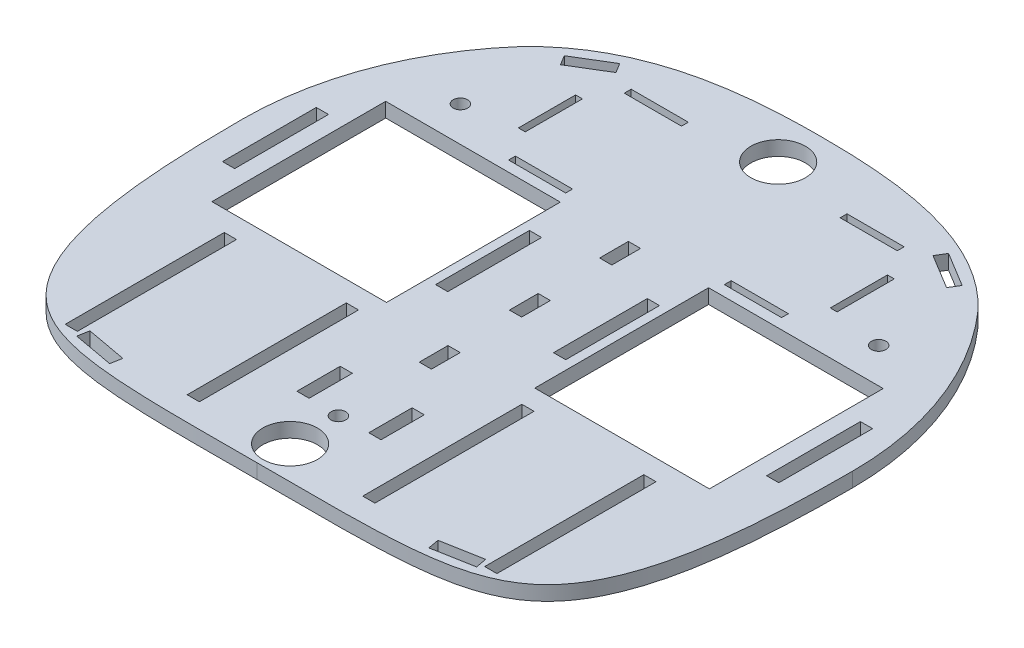
SolidWorks part; units mm, degrees
ref_plane "Front Plane" through (0, 0, 0) normal (0, 0, 1) x (1, 0, 0)
ref_plane "Top Plane" through (0, 0, 0) normal (0, 1, 0) x (1, 0, 0)
ref_plane "Right Plane" through (0, 0, 0) normal (1, 0, 0) x (0, 0, -1)
sketch "Sketch1" plane through (0, 0, 0) normal (0, 1, 0) x (1, 0, 0)
  line L0 (0, 0) -> (-157.9039, -157.9039) construction
  line L1 (0, -127) -> (0, 133.35) construction
  arc A0 (133.35, 0) -> (-133.35, 0) centre (0, 0) ccw
  spline S0 degree 3 poles (-133.35, 0) (-133.35, -51.198) (-123.8034, -129.8051) (-58.428, -127) (0, -127) knots 0 0 0 0 0.502616 1 1 1 1
  spline S1 degree 3 poles (133.35, 0) (133.35, -51.198) (123.8034, -129.8051) (58.428, -127) (0, -127) knots 0 0 0 0 0.502616 1 1 1 1
  dimension "D1" = 266.7
extrude "Base" add sketch "Sketch1" along normal blind 6.35
sketch "ShaftLayout" plane through (0, 6.35, 0) normal (0, 1, 0) x (1, 0, 0)
  line L0 (-133.35, 0) -> (133.35, 0) construction
  line L1 (0, 133.35) -> (0, -127) construction
  line L2 (-114.7053, -6.35) -> (-104.7993, -6.35)
  line L3 (-36.3853, -38) -> (-94.3853, -38)
  line L4 (-36.3853, -38) -> (-36.3853, 38)
  line L5 (-36.3853, 38) -> (-94.3853, 38)
  line L6 (-94.3853, -38) -> (-94.3853, 38)
  line L7 (-36.3853, -38) -> (-94.3853, 38) construction
  line L8 (-36.3853, 38) -> (-94.3853, -38) construction
  line L9 (-102.0053, -15.875) -> (-104.7993, -15.875)
  line L10 (-102.0053, -15.875) -> (-102.0053, 15.875)
  line L11 (-102.0053, 15.875) -> (-104.7993, 15.875)
  line L12 (-104.7993, -15.875) -> (-104.7993, 15.875)
  line L13 (-102.0053, -15.875) -> (-104.7993, 15.875) construction
  line L14 (-102.0053, 15.875) -> (-104.7993, -15.875) construction
  line L15 (-114.7053, -6.35) -> (-114.7053, 6.35)
  line L16 (-104.7993, -6.35) -> (-104.7993, 6.35)
  line L17 (-114.7053, 6.35) -> (-104.7993, 6.35)
  line L18 (-114.7053, -6.35) -> (-104.7993, 6.35) construction
  line L19 (-104.7993, -6.35) -> (-114.7053, 6.35) construction
  line L20 (-116.2928, -9.525) -> (-114.7053, -9.525)
  line L21 (-116.2928, -9.525) -> (-116.2928, 9.525)
  line L22 (-114.7053, -9.525) -> (-114.7053, 9.525)
  line L23 (-116.2928, 9.525) -> (-114.7053, 9.525)
  line L24 (-116.2928, -9.525) -> (-114.7053, 9.525) construction
  line L25 (-114.7053, -9.525) -> (-116.2928, 9.525) construction
  line L26 (-127.4053, -7.9375) -> (-116.2928, -7.9375)
  line L27 (-127.4053, -7.9375) -> (-127.4053, 7.9375)
  line L28 (-116.2928, -7.9375) -> (-116.2928, 7.9375)
  line L29 (-127.4053, 7.9375) -> (-116.2928, 7.9375)
  line L30 (-127.4053, -7.9375) -> (-116.2928, 7.9375) construction
  line L31 (-116.2928, -7.9375) -> (-127.4053, 7.9375) construction
  line L32 (-17.3353, -7.9375) -> (-28.4478, -7.9375)
  line L33 (-30.0353, -9.525) -> (-28.4478, -9.525)
  line L34 (-30.0353, -9.525) -> (-30.0353, 9.525)
  line L35 (-30.0353, 9.525) -> (-28.4478, 9.525)
  line L36 (-28.4478, -9.525) -> (-28.4478, 9.525)
  line L37 (-30.0353, -9.525) -> (-28.4478, 9.525) construction
  line L38 (-30.0353, 9.525) -> (-28.4478, -9.525) construction
  line L39 (-17.3353, -7.9375) -> (-17.3353, 7.9375)
  line L40 (-28.4478, -7.9375) -> (-28.4478, 7.9375)
  line L41 (-17.3353, 7.9375) -> (-28.4478, 7.9375)
  line L42 (-17.3353, -7.9375) -> (-28.4478, 7.9375) construction
  line L43 (-28.4478, -7.9375) -> (-17.3353, 7.9375) construction
  line L45 (-67.3853, -10.033) -> (-56.3853, -10.033)
  line L46 (-67.3853, -10.033) -> (-67.3853, 10.033)
  line L47 (-67.3853, 10.033) -> (-56.3853, 10.033)
  line L48 (-56.3853, -10.033) -> (-56.3853, 10.033)
  line L49 (-67.3853, -10.033) -> (-56.3853, 10.033) construction
  line L50 (-67.3853, 10.033) -> (-56.3853, -10.033) construction
  arc A0 (133.35, 0) -> (-133.35, 0) centre (0, 0) ccw construction
  point P10 (-65.3853, 0)
  point P15 (-103.4023, 0)
  point P20 (-29.2416, 0)
  point P21 (-109.7523, 0)
  point P22 (-115.4991, 0)
  point P23 (-121.8491, 0)
  point P40 (-61.8853, 0)
  point P41 (-22.8916, 0)
  dimension "D1" = 58
  dimension "D2" = 76
  dimension "D3" = 7.62
  dimension "D4" = 2.794
  dimension "D5" = 31.75
  dimension "D6" = 9.906
  dimension "D7" = 12.7
  dimension "D8" = 19.05
  dimension "D9" = 1.5875
  dimension "D10" = 12.7
  dimension "D11" = 15.875
  dimension "D12" = 19.05
  dimension "D13" = 1.5875
  dimension "D14" = 15.875
  dimension "D15" = 12.7
  dimension "D16" = 6.35
  dimension "D17" = 20.066
  dimension "D18" = 20
  dimension "D19" = 11
sketch "MotorLayout" plane through (0, 6.35, 0) normal (0, 1, 0) x (1, 0, 0)
  line L0 (-94.3853, -81.74) -> (-114.3853, -81.74) construction
  line L1 (-94.3853, -110.24) -> (-18.3853, -110.24)
  line L2 (-94.3853, -110.24) -> (-94.3853, -53.24)
  line L3 (-94.3853, -53.24) -> (-18.3853, -53.24)
  line L4 (-18.3853, -110.24) -> (-18.3853, -53.24)
  line L5 (-94.3853, -110.24) -> (-18.3853, -53.24) construction
  line L6 (-94.3853, -53.24) -> (-18.3853, -110.24) construction
  line L7 (-114.7053, -92.0587) -> (-104.7993, -92.0587)
  line L8 (-104.7993, -97.615) -> (-102.0053, -97.615)
  line L9 (-104.7993, -97.615) -> (-104.7993, -65.865)
  line L10 (-104.7993, -65.865) -> (-102.0053, -65.865)
  line L11 (-102.0053, -97.615) -> (-102.0053, -65.865)
  line L12 (-104.7993, -97.615) -> (-102.0053, -65.865) construction
  line L13 (-104.7993, -65.865) -> (-102.0053, -97.615) construction
  line L14 (-36.3853, -38) -> (-94.3853, -38) construction
  line L15 (-114.7053, -92.0587) -> (-114.7053, -71.4212)
  line L16 (-104.7993, -92.0587) -> (-104.7993, -71.4212)
  line L17 (-114.7053, -71.4212) -> (-104.7993, -71.4212)
  line L18 (-114.7053, -92.0587) -> (-104.7993, -71.4212) construction
  line L19 (-104.7993, -92.0587) -> (-114.7053, -71.4212) construction
  line L20 (-103.4023, -1000) -> (-103.4023, 49000) construction
  line L21 (-34.8953, -53.24) -> (-34.8953, -110.24) construction
  point P0 (-56.3853, -81.74)
  point P7 (-103.4023, -81.74)
  point P14 (-109.7523, -81.74)
  dimension "D1" = 20
  dimension "D2" = 76
  dimension "D3" = 57
  dimension "D4" = 2.794
  dimension "D5" = 15.24
  dimension "D6" = 31.75
  dimension "D7" = 20.6375
  dimension "D8" = 12.7
  dimension "D9" = 7.62
  dimension "D10" = 16.51
sketch "Sketch6" plane through (0, 6.35, 0) normal (0, 1, 0) x (1, 0, 0)
  line L0 (-36.3853, -38) -> (-36.3853, 38) construction
  line L1 (-32.4166, -38) -> (-108.7681, -38)
  line L2 (-32.4166, -38) -> (-32.4166, 38)
  line L3 (-32.4166, 38) -> (-108.7681, 38)
  line L4 (-108.7681, -38) -> (-108.7681, 38)
  line L5 (-28.4478, -9.525) -> (-28.4478, 9.525) construction
  line L6 (-104.7993, -15.875) -> (-104.7993, 15.875) construction
  line L7 (0, 133.35) -> (0, -127) construction
  line L8 (28.4478, 20.5105) -> (23.1138, -20.5105) construction
  line L9 (28.4478, -20.5105) -> (23.1138, 20.5105) construction
  line L10 (116.2928, 20.5105) -> (121.6268, -20.5105) construction
  line L11 (116.2928, -20.5105) -> (121.6268, 20.5105) construction
  line L12 (-133.35, 0) -> (133.35, 0) construction
  line L13 (-116.2928, -20.5105) -> (-121.6268, -20.5105)
  line L14 (-116.2928, -20.5105) -> (-116.2928, 20.5105)
  line L15 (-116.2928, 20.5105) -> (-121.6268, 20.5105)
  line L16 (-121.6268, -20.5105) -> (-121.6268, 20.5105)
  line L17 (-116.2928, -20.5105) -> (-121.6268, 20.5105) construction
  line L18 (-116.2928, 20.5105) -> (-121.6268, -20.5105) construction
  line L19 (-116.2928, -9.525) -> (-116.2928, 9.525) construction
  line L20 (-127.4053, 7.9375) -> (-116.2928, 7.9375) construction
  line L21 (-17.3353, 7.9375) -> (-28.4478, 7.9375) construction
  line L22 (-28.4478, -20.5105) -> (-23.1138, -20.5105)
  line L23 (-28.4478, -20.5105) -> (-28.4478, 20.5105)
  line L24 (-28.4478, 20.5105) -> (-23.1138, 20.5105)
  line L25 (-23.1138, -20.5105) -> (-23.1138, 20.5105)
  line L26 (-28.4478, -20.5105) -> (-23.1138, 20.5105) construction
  line L27 (-28.4478, 20.5105) -> (-23.1138, -20.5105) construction
  line L28 (23.1138, -20.5105) -> (23.1138, 20.5105)
  line L29 (28.4478, 20.5105) -> (23.1138, 20.5105)
  line L30 (28.4478, -20.5105) -> (28.4478, 20.5105)
  line L31 (28.4478, -20.5105) -> (23.1138, -20.5105)
  line L32 (121.6268, -20.5105) -> (121.6268, 20.5105)
  line L33 (116.2928, 20.5105) -> (121.6268, 20.5105)
  line L34 (116.2928, -20.5105) -> (116.2928, 20.5105)
  line L35 (116.2928, -20.5105) -> (121.6268, -20.5105)
  line L36 (108.7681, -38) -> (108.7681, 38)
  line L37 (32.4166, 38) -> (108.7681, 38)
  line L38 (32.4166, -38) -> (32.4166, 38)
  line L39 (32.4166, -38) -> (108.7681, -38)
  point P16 (-118.9598, 0)
  point P27 (-25.7808, 0)
  point P44 (25.7808, 0)
  point P45 (118.9598, 0)
  dimension "D1" = 3.9688
  dimension "D2" = 3.9688
  dimension "D3" = 12.573
  dimension "D4" = 12.573
  dimension "D5" = 5.334
  dimension "D6" = 5.334
extrude "WheelShaftCut" cut sketch "Sketch6" against normal through all
sketch "Sketch8" plane through (0, 6.35, 0) normal (0, 1, 0) x (1, 0, 0)
  line L0 (-94.3853, -81.74) -> (-18.3853, -81.74) construction
  line L1 (-18.3853, -110.24) -> (-18.3853, -53.24) construction
  line L2 (-94.3853, -53.24) -> (-18.3853, -53.24) construction
  line L3 (-35.7113, -116.5265) -> (-41.0453, -116.5265)
  line L4 (-35.7113, -116.5265) -> (-35.7113, -46.9535)
  line L5 (-35.7113, -46.9535) -> (-41.0453, -46.9535)
  line L6 (-41.0453, -116.5265) -> (-41.0453, -46.9535)
  line L7 (-35.7113, -116.5265) -> (-41.0453, -46.9535) construction
  line L8 (-35.7113, -46.9535) -> (-41.0453, -116.5265) construction
  line L9 (18.3853, -72.2785) -> (13.0513, -91.2015) construction
  line L10 (18.3853, -91.2015) -> (13.0513, -72.2785) construction
  line L11 (18.3853, -81.74) -> (15.7183, -81.74) construction
  line L12 (89.0513, -46.9535) -> (94.3853, -116.5265) construction
  line L13 (89.0513, -116.5265) -> (94.3853, -46.9535) construction
  line L14 (35.7113, -46.9535) -> (41.0453, -116.5265) construction
  line L15 (-89.0513, -116.5265) -> (-94.3853, -116.5265)
  line L16 (-89.0513, -116.5265) -> (-89.0513, -46.9535)
  line L17 (-89.0513, -46.9535) -> (-94.3853, -46.9535)
  line L18 (-94.3853, -116.5265) -> (-94.3853, -46.9535)
  line L19 (-89.0513, -116.5265) -> (-94.3853, -46.9535) construction
  line L20 (-89.0513, -46.9535) -> (-94.3853, -116.5265) construction
  line L21 (-94.3853, -110.24) -> (-94.3853, -53.24) construction
  line L22 (0, 133.35) -> (0, -127) construction
  line L23 (35.7113, -116.5265) -> (41.0453, -46.9535) construction
  line L24 (94.3853, -81.74) -> (18.3853, -81.74) construction
  line L25 (13.0513, -91.2015) -> (13.0513, -72.2785)
  line L26 (18.3853, -72.2785) -> (13.0513, -72.2785)
  line L27 (18.3853, -91.2015) -> (18.3853, -72.2785)
  line L28 (18.3853, -91.2015) -> (13.0513, -91.2015)
  line L29 (94.3853, -116.5265) -> (94.3853, -46.9535)
  line L30 (89.0513, -46.9535) -> (94.3853, -46.9535)
  line L31 (89.0513, -116.5265) -> (89.0513, -46.9535)
  line L32 (89.0513, -116.5265) -> (94.3853, -116.5265)
  line L33 (41.0453, -116.5265) -> (41.0453, -46.9535)
  line L34 (35.7113, -46.9535) -> (41.0453, -46.9535)
  line L35 (35.7113, -116.5265) -> (35.7113, -46.9535)
  line L36 (35.7113, -116.5265) -> (41.0453, -116.5265)
  line L37 (-94.3853, -110.24) -> (-18.3853, -110.24) construction
  line L42 (-18.3853, -81.74) -> (-15.7183, -81.74) construction
  line L44 (-18.3853, -91.2015) -> (-13.0513, -91.2015)
  line L45 (-18.3853, -91.2015) -> (-18.3853, -72.2785)
  line L46 (-18.3853, -72.2785) -> (-13.0513, -72.2785)
  line L47 (-13.0513, -91.2015) -> (-13.0513, -72.2785)
  line L48 (-18.3853, -91.2015) -> (-13.0513, -72.2785) construction
  line L49 (-18.3853, -72.2785) -> (-13.0513, -91.2015) construction
  point P6 (-63.7079, -81.74)
  point P7 (-38.2513, -81.74)
  point P19 (-91.5913, -81.74)
  point P39 (91.5913, -81.74)
  point P40 (38.2513, -81.74)
  dimension "D1" = 5.334
  dimension "D2" = 6.2865
  dimension "D4" = 5.334
  dimension "D5" = 18.923
  dimension "D6" = 6.2865
  dimension "D3" = 2
extrude "MotorCut" cut sketch "Sketch8" against normal through all
sketch "BatteryLayout" plane through (0, 6.35, 0) normal (0, 1, 0) x (1, 0, 0)
  line L0 (0, 133.35) -> (0, -127) construction
  line L1 (-32.4166, 38) -> (-108.7681, 38) construction
  line L2 (-66.675, 45.62) -> (66.675, 45.62)
  line L3 (-66.675, 45.62) -> (-66.675, 93.245)
  line L4 (-66.675, 93.245) -> (66.675, 93.245)
  line L5 (66.675, 45.62) -> (66.675, 93.245)
  line L6 (-66.675, 45.62) -> (66.675, 93.245) construction
  line L7 (-66.675, 93.245) -> (66.675, 45.62) construction
  arc A0 (133.35, 0) -> (-133.35, 0) centre (0, 0) ccw construction
  point P6 (0, 69.4325)
  dimension "D1" = 133.35
  dimension "D2" = 47.625
  dimension "D3" = 7.62
sketch "Sketch10" plane through (0, 6.35, 0) normal (0, 1, 0) x (1, 0, 0)
  line L0 (-66.675, 93.245) -> (66.675, 93.245) construction
  line L1 (-59.69, 42.62) -> (-34.69, 42.62)
  line L2 (-59.69, 42.62) -> (-59.69, 45.62)
  line L3 (-59.69, 45.62) -> (-34.69, 45.62)
  line L4 (-34.69, 42.62) -> (-34.69, 45.62)
  line L5 (-59.69, 42.62) -> (-34.69, 45.62) construction
  line L6 (-59.69, 45.62) -> (-34.69, 42.62) construction
  line L7 (-59.69, 96.245) -> (-34.69, 96.245)
  line L8 (-59.69, 96.245) -> (-59.69, 93.245)
  line L9 (-59.69, 93.245) -> (-34.69, 93.245)
  line L10 (-34.69, 96.245) -> (-34.69, 93.245)
  line L11 (-59.69, 96.245) -> (-34.69, 93.245) construction
  line L12 (-59.69, 93.245) -> (-34.69, 96.245) construction
  line L13 (-66.675, 45.62) -> (66.675, 45.62) construction
  line L14 (-66.675, 45.62) -> (-66.675, 93.245) construction
  line L15 (0, 69.4325) -> (-66.675, 69.4325) construction
  line L16 (-66.675, 56.9325) -> (-69.675, 56.9325)
  line L17 (-66.675, 56.9325) -> (-66.675, 81.9325)
  line L18 (-66.675, 81.9325) -> (-69.675, 81.9325)
  line L19 (-69.675, 56.9325) -> (-69.675, 81.9325)
  line L20 (0, 133.35) -> (0, -127) construction
  line L21 (59.69, 93.245) -> (34.69, 96.245) construction
  line L22 (59.69, 96.245) -> (34.69, 93.245) construction
  line L23 (59.69, 45.62) -> (34.69, 42.62) construction
  line L24 (59.69, 42.62) -> (34.69, 45.62) construction
  line L25 (69.675, 56.9325) -> (69.675, 81.9325)
  line L26 (66.675, 81.9325) -> (69.675, 81.9325)
  line L27 (66.675, 56.9325) -> (66.675, 81.9325)
  line L28 (66.675, 56.9325) -> (69.675, 56.9325)
  line L29 (34.69, 96.245) -> (34.69, 93.245)
  line L30 (59.69, 93.245) -> (34.69, 93.245)
  line L31 (59.69, 96.245) -> (59.69, 93.245)
  line L32 (59.69, 96.245) -> (34.69, 96.245)
  line L33 (34.69, 42.62) -> (34.69, 45.62)
  line L34 (59.69, 45.62) -> (34.69, 45.62)
  line L35 (59.69, 42.62) -> (59.69, 45.62)
  line L36 (59.69, 42.62) -> (34.69, 42.62)
  point P0 (-47.19, 44.12)
  point P5 (-47.19, 94.745)
  point P20 (-66.675, 69.4325)
  point P40 (66.675, 69.4325)
  point P41 (47.19, 94.745)
  point P42 (47.19, 44.12)
  dimension "D1" = 3
  dimension "D2" = 3
  dimension "D3" = 25
  dimension "D4" = 25
  dimension "D5" = 6.985
  dimension "D6" = 6.985
  dimension "D7" = 3
  dimension "D8" = 25
extrude "VelcroCut" cut sketch "Sketch10" against normal through all
sketch "Sketch11" plane through (0, 6.35, 0) normal (0, 1, 0) x (1, 0, 0)
  line L0 (0, 133.35) -> (0, -127) construction
  line L1 (-133.35, 0) -> (133.35, 0) construction
  circle A1 centre (0, -91.44) radius 3.175
  circle A2 centre (-91.44, 53.34) radius 3.175
  circle A3 centre (91.44, 53.34) radius 3.175
  dimension "D1" = 6.35
  dimension "D2" = 53.34
  dimension "D3" = 6.35
  dimension "D6" = 91.44
  dimension "D4" = 91.44
extrude "ScrewCut" cut sketch "Sketch11" against normal through all
sketch "Sketch13" plane through (0, 6.35, 0) normal (0, 1, 0) x (1, 0, 0)
  line L0 (0, 133.35) -> (0, -127) construction
  line L1 (-2.667, 25.427) -> (2.667, 25.427)
  line L2 (-2.667, 25.427) -> (-2.667, 38)
  line L3 (-2.667, 38) -> (2.667, 38)
  line L4 (2.667, 25.427) -> (2.667, 38)
  line L5 (-2.667, 25.427) -> (2.667, 38) construction
  line L6 (-2.667, 38) -> (2.667, 25.427) construction
  line L7 (108.7681, 38) -> (32.4166, 38) construction
  line L8 (-2.667, -14.0065) -> (2.667, -14.0065)
  line L9 (-2.667, -14.0065) -> (-2.667, -1.4335)
  line L10 (-2.667, -1.4335) -> (2.667, -1.4335)
  line L11 (2.667, -14.0065) -> (2.667, -1.4335)
  line L12 (-2.667, -14.0065) -> (2.667, -1.4335) construction
  line L13 (-2.667, -1.4335) -> (2.667, -14.0065) construction
  line L14 (-2.667, -53.44) -> (2.667, -53.44)
  line L15 (-2.667, -53.44) -> (-2.667, -40.867)
  line L16 (-2.667, -40.867) -> (2.667, -40.867)
  line L17 (2.667, -53.44) -> (2.667, -40.867)
  line L18 (-2.667, -53.44) -> (2.667, -40.867) construction
  line L19 (-2.667, -40.867) -> (2.667, -53.44) construction
  point P0 (0, 31.7135)
  point P10 (0, -7.72)
  point P15 (0, -47.1535)
  dimension "D1" = 5.334
  dimension "D2" = 12.573
  dimension "D3" = 0
  dimension "D5" = 91.44
  dimension "D4" = 3
extrude "SupportStrutCut" cut sketch "Sketch13" against normal through all
sketch "Sketch16" plane through (0, 6.35, 0) normal (0, 1, 0) x (1, 0, 0)
  line L0 (0, -1000) -> (0, 49000) construction
  line L1 (-100.0331, 133.35) -> (-100.0331, 88.1793)
  line L2 (-100.0331, 133.35) -> (100.0331, 133.35)
  line L3 (100.0331, 133.35) -> (100.0331, 88.1793)
  arc A0 (133.35, 0) -> (-133.35, 0) centre (0, 0) ccw construction
  spline S0 degree 3 poles (-100.0331, 88.1793) (-73.9195, 115.9102) (-34.9729, 119.8228) (0, 119.8228) knots 0 0 0 0 1 1 1 1
  spline S1 degree 3 poles (100.0331, 88.1793) (73.9195, 115.9102) (34.9729, 119.8228) (0, 119.8228) knots 0 0 0 0 1 1 1 1
extrude "EmptySpaceTrim" cut sketch "Sketch16" against normal through all
sketch "Sketch15" plane through (0, 6.35, 0) normal (0, 1, 0) x (1, 0, 0)
  line L0 (-78.1477, -1116.59) -> (-78.1477, 48883.41) construction
  line L2 (-87.4187, -118.4593) -> (-69.7657, -121.6799)
  line L3 (-87.4187, -118.4593) -> (-86.5298, -113.5867)
  line L4 (-69.7657, -121.6799) -> (-68.8768, -116.8073)
  line L5 (-86.5298, -113.5867) -> (-68.8768, -116.8073)
  line L6 (-87.4187, -118.4593) -> (-68.8768, -116.8073) construction
  line L7 (-69.7657, -121.6799) -> (-86.5298, -113.5867) construction
  line L8 (-84.4066, 90.0604) -> (-69.3179, 99.2234)
  line L9 (-84.4066, 90.0604) -> (-86.9775, 94.2939)
  line L10 (-69.3179, 99.2234) -> (-71.8889, 103.4569)
  line L11 (-86.9775, 94.2939) -> (-71.8889, 103.4569)
  line L12 (-84.4066, 90.0604) -> (-71.8889, 103.4569) construction
  line L13 (-69.3179, 99.2234) -> (-86.9775, 94.2939) construction
  line L14 (0, -1000) -> (0, 49000) construction
  line L15 (69.3179, 99.2234) -> (86.9775, 94.2939) construction
  line L16 (84.4066, 90.0604) -> (71.8889, 103.4569) construction
  line L17 (69.7657, -121.6799) -> (86.5298, -113.5867) construction
  line L18 (87.4187, -118.4593) -> (68.8768, -116.8073) construction
  line L19 (88.7973, -116.59) -> (66.5019, -116.59) construction
  line L20 (86.9775, 94.2939) -> (71.8889, 103.4569)
  line L21 (69.3179, 99.2234) -> (71.8889, 103.4569)
  line L22 (84.4066, 90.0604) -> (86.9775, 94.2939)
  line L23 (84.4066, 90.0604) -> (69.3179, 99.2234)
  line L24 (86.5298, -113.5867) -> (68.8768, -116.8073)
  line L25 (69.7657, -121.6799) -> (68.8768, -116.8073)
  line L26 (87.4187, -118.4593) -> (86.5298, -113.5867)
  line L27 (87.4187, -118.4593) -> (69.7657, -121.6799)
  point P4 (-78.1477, 96.7587)
  point P7 (-78.1477, -117.6333)
  point P30 (78.1477, -117.6333)
  point P31 (78.1477, 96.7587)
  dimension "D1" = 4.953
  dimension "D2" = 17.653
  dimension "D3" = 17.653
  dimension "D4" = 4.953
extrude "TapeSensorCut" cut sketch "Sketch15" against normal through all
sketch "Sketch17" plane through (0, 6.35, 0) normal (0, 1, 0) x (1, 0, 0)
  line L0 (0, -1000) -> (0, 49000) construction
  line L1 (-34.69, 93.245) -> (34.69, 93.245) construction
  circle A0 centre (0, 100.8346) radius 11.938
  circle A1 centre (0, 100.8346) radius 5 construction
  circle A2 centre (0, -112.5625) radius 11.938
  dimension "D1" = 23.876
  dimension "D2" = 10
  dimension "D3" = 23.876
extrude "CasterCut" cut sketch "Sketch17" against normal through all
sketch "Layer1Limits" plane through (0, 0, 0) normal (0, 1, 0) x (1, 0, 0)
  line L0 (-127, 119.8228) -> (127, -134.1772) construction
  line L1 (-127, -134.1772) -> (127, -134.1772) construction
  line L2 (-127, -134.1772) -> (-127, 119.8228) construction
  line L3 (-127, 119.8228) -> (127, 119.8228) construction
  line L4 (127, -134.1772) -> (127, 119.8228) construction
  line L5 (127, 119.8228) -> (-127, -134.1772) construction
  line L6 (0, -1000) -> (0, 49000) construction
  point P4 (0, -7.1772)
  dimension "D1" = 254
  dimension "D2" = 254
